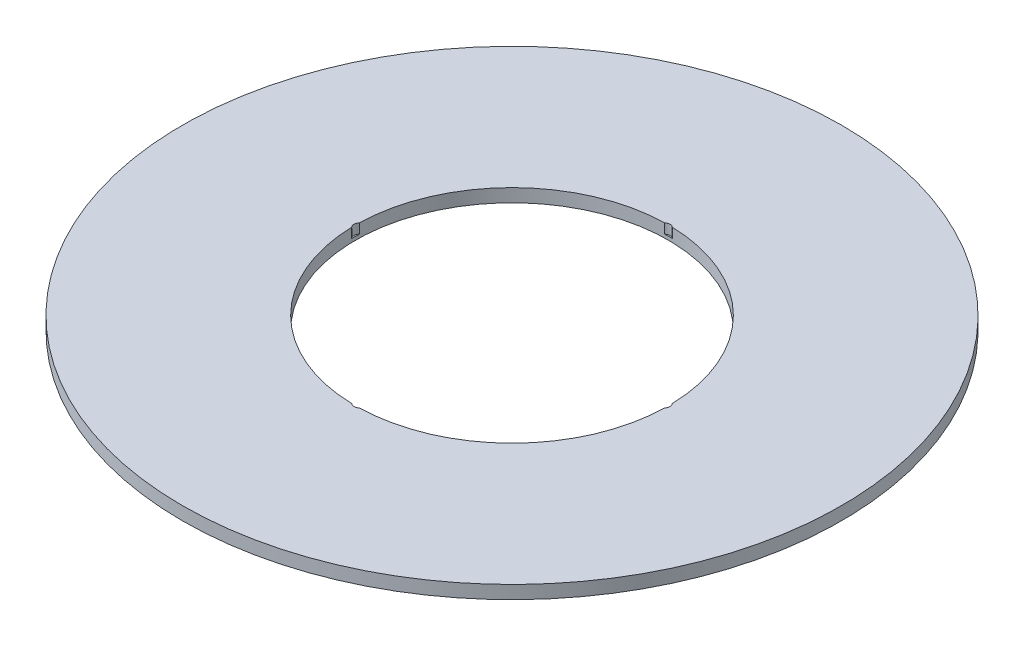
SolidWorks part; units mm, degrees
ref_plane "Front Plane" through (0, 0, 0) normal (0, 0, 1) x (1, 0, 0)
ref_plane "Top Plane" through (0, 0, 0) normal (0, 1, 0) x (1, 0, 0)
ref_plane "Right Plane" through (0, 0, 0) normal (1, 0, 0) x (0, 0, -1)
sketch "Sketch1" plane through (0, 0, 0) normal (0, 1, 0) x (1, 0, 0)
  circle A0 centre (0, 0) radius 100
  dimension "FLANGE_OD" = 200
extrude "Boss-Extrude1" add sketch "Sketch1" along normal blind 4
sketch "Sketch2" plane through (0, 0, 0) normal (0, 1, 0) x (1, 0, 0)
  circle A0 centre (0, 0) radius 47.5
  dimension "BORE_D" = 95
extrude "Cut-Extrude1" cut sketch "Sketch2" along normal through all
sketch "Sketch3" plane through (0, 4, 0) normal (0, 1, 0) x (1, 0, 0)
  circle A0 centre (0, 0) radius 46.2847 construction
  circle A1 centre (-46.2847, 0) radius 1.658
  dimension "BOLT_D" = 3.316
  dimension "BOLT_PCD" = 92.5693
extrude "Cut-Extrude2" cut sketch "Sketch3" against normal blind 2.974
pattern_circular "CirPattern1" count 4 over 360 about axis through (0, 0, 0) along (0, 1, 0) of "Cut-Extrude2"
